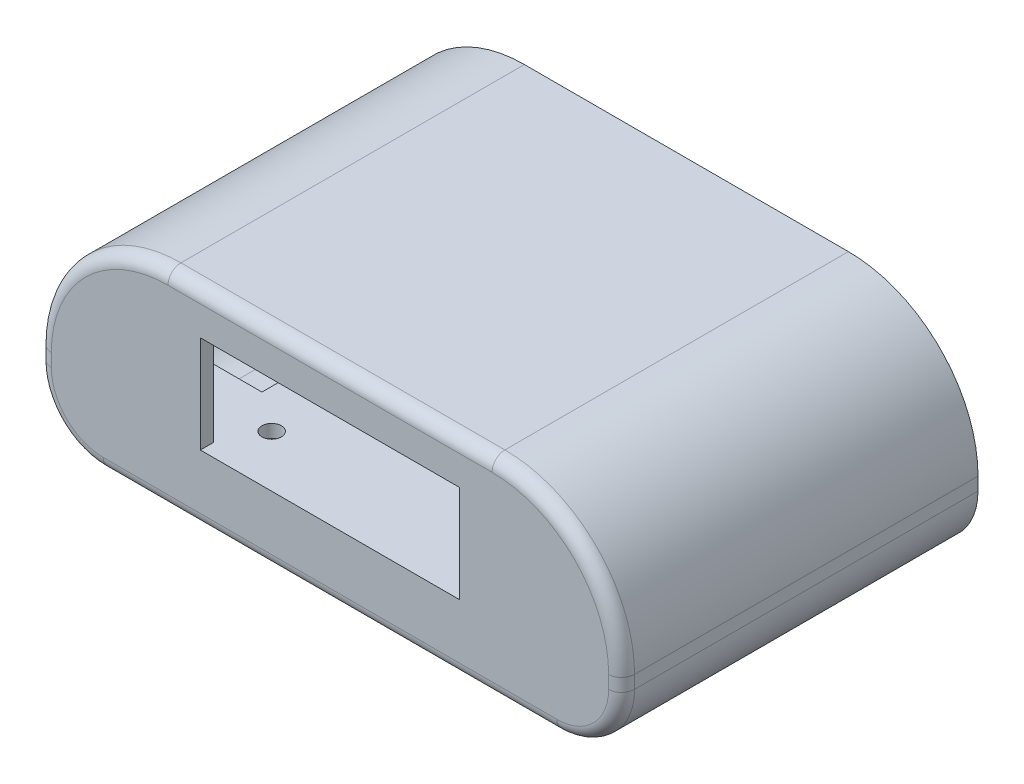
SolidWorks part; units mm, degrees
ref_plane "Front Plane" through (0, 0, 0) normal (0, 0, 1) x (1, 0, 0)
ref_plane "Top Plane" through (0, 0, 0) normal (0, 1, 0) x (1, 0, 0)
ref_plane "Right Plane" through (0, 0, 0) normal (1, 0, 0) x (0, 0, -1)
sketch "Sketch1" plane through (0, 0, 0) normal (0, 0, 1) x (1, 0, 0)
  line L1 (-25, 16) -> (25, 16)
  line L2 (-45, -4) -> (-45, -6)
  line L3 (-35, -16) -> (35, -16)
  line L4 (45, -4) -> (45, -6)
  line L5 (-45, 16) -> (45, -16) construction
  line L6 (-45, -16) -> (45, 16) construction
  arc A0 (35, -16) -> (45, -6) centre (35, -6) ccw
  arc A1 (-45, -6) -> (-35, -16) centre (-35, -6) ccw
  arc A2 (25, 16) -> (45, -4) centre (25, -4) cw
  arc A3 (-25, 16) -> (-45, -4) centre (-25, -4) ccw
  point P0 (0, 0)
  dimension "D1" = 20
  dimension "D4" = 10
  dimension "D2" = 90
  dimension "D3" = 32
extrude "Boss-Extrude1" add sketch "Sketch1" along normal blind 55
shell "Shell1" thickness 2 removed face at (0, -1.9822, 0)
sketch "Sketch2" plane through (0, 0, 0) normal (0, 0, -1) x (-1, 0, 0)
  line L0 (-25, 16) -> (25, 16) construction
  line L1 (-17, 4.48) -> (-40.8773, 4.48)
  line L2 (-17, 4.48) -> (-17, 14)
  line L3 (0, 14) -> (0, -14) construction
  line L4 (-25, 14) -> (25, 14) construction
  line L5 (35, -14) -> (-35, -14) construction
  line L7 (17, 4.48) -> (40.8773, 4.48)
  line L8 (-17, 14) -> (-25, 14)
  line L9 (-45, -6) -> (-45, -4) construction
  line L10 (17, 4.48) -> (17, 14)
  line L11 (17, 14) -> (25, 14)
  arc A0 (-25, 14) -> (-43, -4) centre (-25, -4) ccw construction
  arc A1 (-40.8773, 4.48) -> (-25, 14) centre (-25, -4) cw
  arc A2 (40.8773, 4.48) -> (25, 14) centre (25, -4) ccw
  point P22 (-45, -5)
  dimension "D1" = 11.52
  dimension "D2" = 28
extrude "Boss-Extrude2" add sketch "Sketch2" against normal blind 10 contours L7 A2 L11 L10 | L1 A1 L8 L2
hole_wizard "M3x0.5 Tapped Hole1" positions "Sketch3" profile "Sketch4" tap size "M3x0.5" standard "ANSI Metric"
sketch "Sketch3" plane through (0, 0, 0) normal (0, 0, -1) x (-1, 0, 0)
  line L0 (-25, 16) -> (25, 16) construction
  line L1 (-45, -6) -> (-45, -4) construction
  line L2 (45, -4) -> (45, -6) construction
  point P0 (-20, 8)
  point P10 (20, 8)
  dimension "D1" = 8
  dimension "D2" = 25
  dimension "D3" = 25
sketch "Sketch4" plane through (20, 8, 0) normal (1, 0, 0) x (0, 1, 0)
  line L0 (0, 0) -> (0, 8.2511)
  line L1 (0, 8.2511) -> (1.25, 7.5)
  line L2 (1.25, 7.5) -> (1.25, 0)
  line L5 (1.25, 0) -> (0, 0)
  line L10 (0, 8.2511) -> (-1.25, 7.5) construction
  line L11 (0, -6.35) -> (0, 107.95) construction
  dimension "Tap Drill Dia." = 2.5
  dimension "Tap Drill Depth" = 7.5
  dimension "Drill Angle" = 118
sketch "Sketch5" plane through (0, 0, 0) normal (0, 0, -1) x (-1, 0, 0)
  line L0 (-43, -6) -> (-43, -4) construction
  line L1 (-43, -5.52) -> (43, -5.52)
  line L2 (-43, -5.52) -> (-43, -7.52)
  line L3 (-43, -7.52) -> (43, -7.52)
  line L4 (43, -5.52) -> (43, -7.52)
  line L5 (43, -4) -> (43, -6) construction
  line L7 (-25, 16) -> (25, 16) construction
  dimension "D1" = 21.52
  dimension "D2" = 2
extrude "Boss-Extrude3" add sketch "Sketch5" against normal up to next contours L1 L4 L3 L2
sketch "Sketch6" plane through (0, 0, 53) normal (0, 0, -1) x (-1, 0, 0)
  line L0 (-43, -5.52) -> (43, -5.52) construction
  line L1 (-20, -5.52) -> (20, -5.52)
  line L2 (-20, -5.52) -> (-20, 9.48)
  line L3 (-20, 9.48) -> (20, 9.48)
  line L4 (20, -5.52) -> (20, 9.48)
  point P6 (0, 9.48)
  dimension "D1" = 15
  dimension "D2" = 40
extrude "Cut-Extrude1" cut sketch "Sketch6" against normal blind 10
hole_wizard "Ø3.0mm Dowel Hole1" positions "Sketch7" profile "Sketch8" hole size "Ø3.0" standard "AS"
sketch "Sketch7" plane through (0, -5.52, 0) normal (0, 1, 0) x (1, 0, 0)
  line L0 (17, -34.5) -> (-17, -47) construction
  line L2 (-20, -55) -> (20, -55) construction
  line L3 (-17, -47) -> (-17, -22) construction
  point P0 (-17, -47)
  point P2 (-17, -22)
  point P4 (17, -34.5)
  point P11 (0, -40.75)
  point P14 (0, -55)
  point P20 (-17, -34.5)
  dimension "D1" = 25
  dimension "D2" = 34
  dimension "D3" = 8
sketch "Sketch8" plane through (-17, -5.52, 47) normal (1, 0, 0) x (0, 0, 1)
  line L0 (0, 0) -> (0, 4.9013)
  line L1 (0, 4.9013) -> (1.5, 4)
  line L2 (1.5, 4) -> (1.5, 0)
  line L5 (1.5, 0) -> (0, 0)
  line L10 (0, 4.9013) -> (-1.5, 4) construction
  line L11 (0, -6.35) -> (0, 107.95) construction
  dimension "Hole Dia." = 3
  dimension "Hole Depth" = 4
  dimension "Drill Angle" = 118
sketch "Sketch9" plane through (0, -5.52, 0) normal (0, 1, 0) x (1, 0, 0)
  line L0 (-43, -53) -> (-43, 0) construction
  line L1 (-43, -26.5) -> (-23, -26.5)
  line L2 (-43, -26.5) -> (-43, -42.5)
  line L3 (-43, -42.5) -> (-23, -42.5)
  line L4 (-23, -26.5) -> (-23, -42.5)
  line L5 (-17, -47) -> (-17, -22) construction
  point P6 (-17, -34.5)
  point P7 (-23, -34.5)
  dimension "D1" = 20
extrude "Cut-Extrude2" cut sketch "Sketch9" against normal up to surface (2 mm away) up to face at (-17, -7.52, 45.5)
fillet "Fillet1" radius 2 8 edges at (45, -5, 55) (42.0711, -13.0711, 55) (0, -16, 55) (-42.0711, -13.0711, 55) (-45, -5, 55) (-39.1421, 10.1421, 55) (0, 16, 55) (39.1421, 10.1421, 55)
